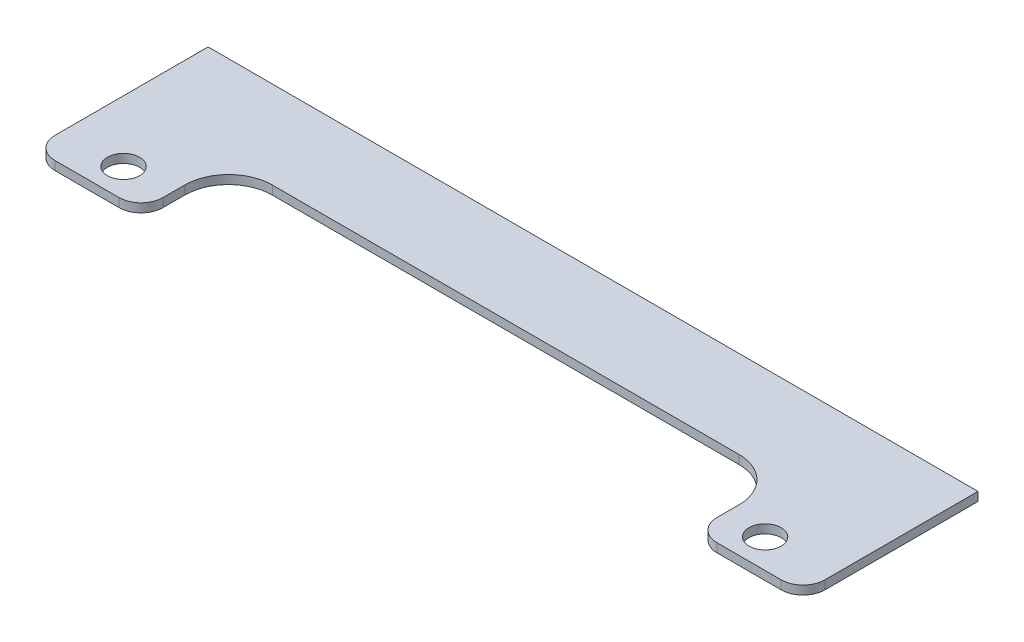
SolidWorks part; units mm, degrees
material "Клен"
ref_plane "Спереди" through (0, 0, 0) normal (0, 0, 1) x (1, 0, 0)
ref_plane "Сверху" through (0, 0, 0) normal (0, 1, 0) x (1, 0, 0)
ref_plane "Справа" through (0, 0, 0) normal (1, 0, 0) x (0, 0, -1)
sketch "Эскиз1" plane through (0, 0, 0) normal (0, 1, 0) x (1, 0, 0)
  line L0 (-338.2029, 15) -> (-338.2029, 120)
  line L5 (-338.2029, 120) -> (189.7971, 120)
  line L6 (189.7971, 120) -> (189.7971, 15)
  line L7 (174.7971, 0) -> (130.7971, 0)
  line L8 (115.7971, 15) -> (115.7971, 30)
  line L9 (85.7971, 60) -> (-234.2029, 60)
  line L10 (-264.2029, 30) -> (-264.2029, 15)
  line L11 (-279.2029, 0) -> (-323.2029, 0)
  arc A0 (-234.2029, 60) -> (-264.2029, 30) centre (-234.2029, 30) ccw
  arc A1 (115.7971, 30) -> (85.7971, 60) centre (85.7971, 30) ccw
  arc A2 (-264.2029, 15) -> (-279.2029, 0) centre (-279.2029, 15) cw
  arc A3 (130.7971, 0) -> (115.7971, 15) centre (130.7971, 15) cw
  arc A4 (-338.2029, 15) -> (-323.2029, 0) centre (-323.2029, 15) ccw
  arc A5 (189.7971, 15) -> (174.7971, 0) centre (174.7971, 15) cw
  point P10 (-264.2029, 22.5)
  point P13 (115.7971, 22.5)
  dimension "D4" = 30
  dimension "D5" = 30
  dimension "D6" = 15
  dimension "D7" = 15
  dimension "D8" = 15
  dimension "D9" = 15
  dimension "D2" = 120
  dimension "D3" = 74
  dimension "D10" = 60
  dimension "D11" = 380
  dimension "D12" = 74
extrude "Бобышка-Вытянуть1" add sketch "Эскиз1" along normal blind 6
sketch "Эскиз7" plane through (0, 0, 0) normal (0, 1, 0) x (1, 0, 0)
  circle A1 centre (-296.2029, 20) radius 11
  dimension "D1" = 22
extrude "Вырез-Вытянуть1" cut sketch "Эскиз7" against normal blind 5 and the other way blind 14
sketch "Эскиз8" plane through (0, 0, 0) normal (0, 1, 0) x (1, 0, 0)
  circle A0 centre (143.7971, 20) radius 11
  point P3 (135.7971, 20)
  dimension "D1" = 22
extrude "Вырез-Вытянуть2" cut sketch "Эскиз8" against normal blind 5 and the other way blind 11
